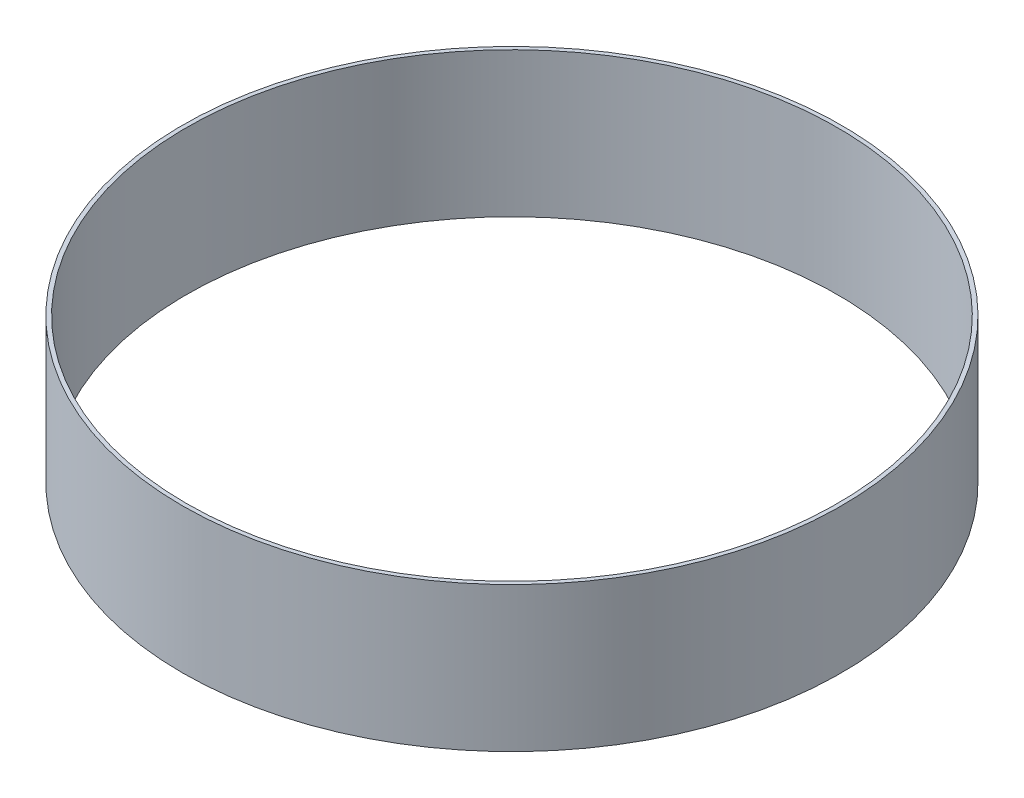
SolidWorks part; units mm, degrees
material "PC High Viscosity"
ref_plane "Front Plane" through (0, 0, 0) normal (0, 0, 1) x (1, 0, 0)
ref_plane "Top Plane" through (0, 0, 0) normal (0, 1, 0) x (1, 0, 0)
ref_plane "Right Plane" through (0, 0, 0) normal (1, 0, 0) x (0, 0, -1)
sketch "Sketch1" plane through (0, 0, 0) normal (0, 1, 0) x (1, 0, 0)
  circle A0 centre (0, 0) radius 260.35
  circle A1 centre (0, 0) radius 257.175
  dimension "D1" = 520.7
  dimension "D2" = 514.35
extrude "Boss-Extrude1" add sketch "Sketch1" along normal blind 114.3
